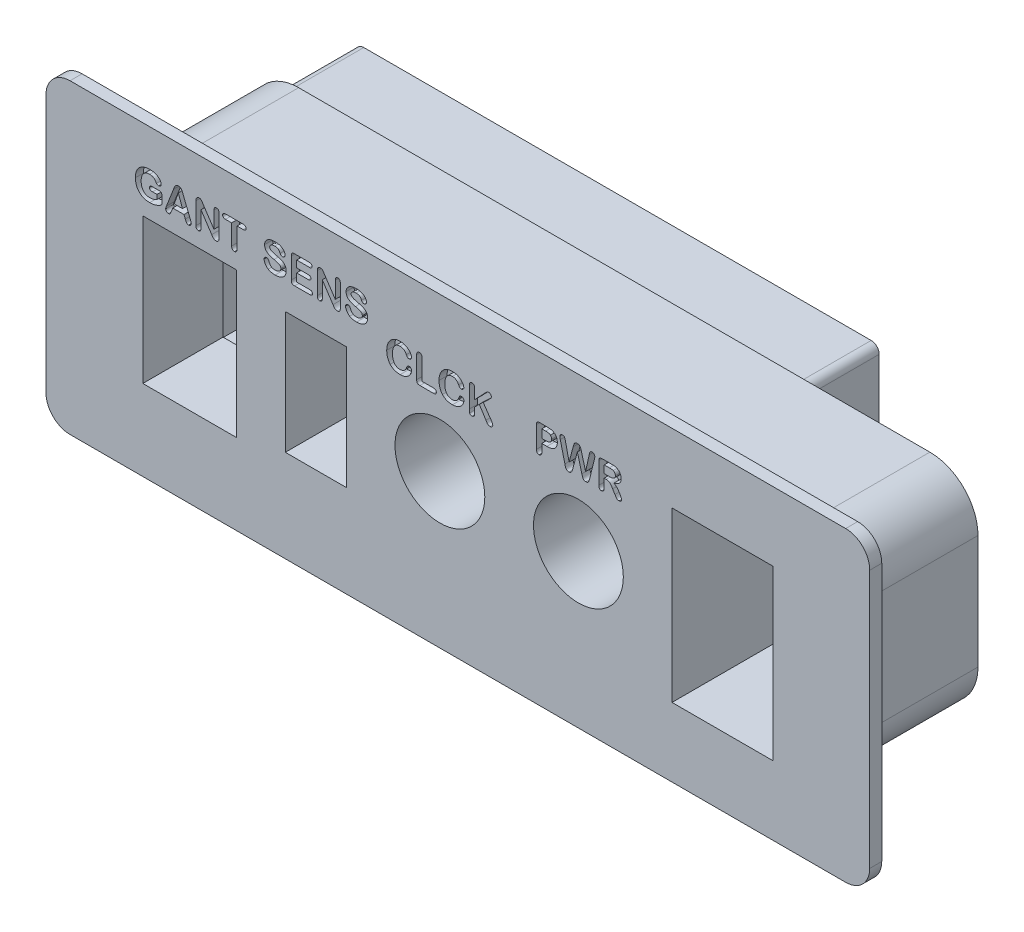
SolidWorks part; units mm, degrees
ref_plane "Front Plane" through (0, 0, 0) normal (0, 0, 1) x (1, 0, 0)
ref_plane "Top Plane" through (0, 0, 0) normal (0, 1, 0) x (1, 0, 0)
ref_plane "Right Plane" through (0, 0, 0) normal (1, 0, 0) x (0, 0, -1)
sketch "Sketch1" plane through (0, 0, 0) normal (0, 0, 1) x (1, 0, 0)
  line L1 (-45.35, -13.1) -> (45.35, -13.1)
  line L2 (-45.35, -13.1) -> (-45.35, 13.1)
  line L3 (-45.35, 13.1) -> (45.35, 13.1)
  line L4 (45.35, -13.1) -> (45.35, 13.1)
  line L5 (-45.35, -13.1) -> (45.35, 13.1) construction
  line L6 (-45.35, 13.1) -> (45.35, -13.1) construction
  point P0 (0, 0)
  dimension "D1" = 90.7
  dimension "D2" = 26.2
extrude "Boss-Extrude1" add sketch "Sketch1" against normal blind 18
sketch "Sketch2" plane through (0, 0, 0) normal (0, 0, 1) x (1, 0, 0)
  line L0 (-45.35, 13.1) -> (-45.35, -13.1) construction
  line L1 (-51.35, -19.1) -> (51.35, -19.1)
  line L2 (-51.35, -19.1) -> (-51.35, 19.1)
  line L3 (-51.35, 19.1) -> (51.35, 19.1)
  line L4 (51.35, -19.1) -> (51.35, 19.1)
  line L5 (-51.35, -19.1) -> (51.35, 19.1) construction
  line L6 (-51.35, 19.1) -> (51.35, -19.1) construction
  line L7 (45.35, 13.1) -> (-45.35, 13.1) construction
  point P0 (0, 0)
  dimension "D1" = 6
  dimension "D2" = 6
extrude "Boss-Extrude2" add sketch "Sketch2" along normal blind 1.5
fillet "Fillet1" radius 6 4 edges at (-45.35, 13.1, -9) (-45.35, -13.1, -9) (45.35, -13.1, -9) (45.35, 13.1, -9)
fillet "Fillet2" radius 3 4 edges at (51.35, -19.1, 0.75) (-51.35, -19.1, 0.75) (-51.35, 19.1, 0.75) (51.35, 19.1, 0.75)
sketch "Sketch3" plane through (0, 0, 1.5) normal (0, 0, 1) x (1, 0, 0)
  line L0 (-45.35, 13.1) -> (45.35, 13.1) construction
  line L1 (-45.35, 13.1) -> (-45.35, -13.1) construction
  line L2 (-45.35, -13.1) -> (45.35, -13.1) construction
  line L3 (45.35, 13.1) -> (45.35, -13.1) construction
  line L4 (-21.51, 7.6) -> (-13.91, 7.6)
  line L5 (-39.28, 9.05) -> (-27.58, 9.05)
  line L6 (-39.28, 9.05) -> (-39.28, -9.05)
  line L7 (-39.28, -9.05) -> (-27.58, -9.05)
  line L8 (-27.58, 9.05) -> (-27.58, -9.05)
  line L9 (-21.51, 7.6) -> (-21.51, -7.6)
  line L10 (-21.51, -7.6) -> (-13.91, -7.6)
  line L11 (-13.91, 7.6) -> (-13.91, -7.6)
  line L12 (-45.35, 0) -> (-39.28, 0) construction
  line L13 (-27.58, 0) -> (-21.51, 0) construction
  line L14 (20.63, 0) -> (26.7, 0) construction
  line L15 (-45.35, 13.1) -> (45.35, -13.1) construction
  line L16 (9.43, 0) -> (3.36, 0) construction
  line L17 (-7.84, 0) -> (-13.91, 0) construction
  line L18 (39.35, 13.1) -> (-39.35, 13.1) construction
  line L19 (39.3, -10.5) -> (26.7, -10.5)
  line L20 (39.3, -10.5) -> (39.3, 10.5)
  line L21 (39.3, 10.5) -> (26.7, 10.5)
  line L22 (26.7, -10.5) -> (26.7, 10.5)
  line L23 (39.3, -10.5) -> (26.7, 10.5) construction
  line L24 (39.3, 10.5) -> (26.7, -10.5) construction
  line L25 (45.35, -7.1) -> (45.35, 7.1) construction
  line L26 (39.3, 0) -> (45.35, 0) construction
  circle A0 centre (15.03, 0) radius 5.6
  circle A1 centre (-2.24, 0) radius 5.6
  point P20 (0, 0)
  point P23 (33, 0)
  dimension "D6" = 11.2
  dimension "D1" = 11.7
  dimension "D2" = 18.1
  dimension "D3" = 6.05
  dimension "D4" = 7.6
  dimension "D5" = 6.07
  dimension "D7" = 12.6
  dimension "D8" = 21
  dimension "D9" = 15.2
extrude "Cut-Extrude1" cut sketch "Sketch3" against normal through all
sketch "Sketch4" plane through (0, 0, 1.5) normal (0, 0, 1) x (1, 0, 0)
  line L0 (-33.43, -9.05) -> (-33.43, 10.95) construction
  line L1 (-39.28, -9.05) -> (-27.58, -9.05) construction
  line L2 (-17.71, -7.6) -> (-17.71, 12.4) construction
  line L3 (-21.51, -7.6) -> (-13.91, -7.6) construction
  line L4 (-40.43, 10.95) -> (-26.43, 10.95) construction
  line L5 (-24.71, 10.95) -> (-10.71, 10.95) construction
  line L6 (-2.24, 0) -> (-2.24, 8) construction
  line L7 (-12.74, 8) -> (8.26, 8) construction
  line L8 (15.03, 0) -> (15.03, 8) construction
  line L9 (4.53, 8) -> (25.53, 8) construction
  text T0 "GANT" font "Arial Rounded MT Bold" height in points 14
  text T1 "SENS" font "Arial Rounded MT Bold" height in points 14
  text T2 "CLCK" font "Arial Rounded MT Bold" height in points 14
  text T3 "PWR" font "Arial Rounded MT Bold" height in points 14
  point P11 (-33.43, 10.95)
  point P13 (-17.71, 10.95)
  point P22 (-2.24, 8)
  point P28 (15.03, 8)
  dimension "D1" = 20
  dimension "D2" = 14
  dimension "D3" = 21
  dimension "D4" = 8
extrude "Cut-Extrude2" cut sketch "Sketch4" against normal blind 1
sketch "Sketch5" plane through (0, 0, -18) normal (0, 0, -1) x (-1, 0, 0)
  line L7 (27.28, 9.4) -> (39.58, 9.4)
  line L8 (27.28, 9.4) -> (27.28, -9.4)
  line L9 (27.28, -9.4) -> (39.58, -9.4)
  line L10 (39.58, 9.4) -> (39.58, -9.4)
  line L11 (27.28, 9.4) -> (39.58, -9.4) construction
  line L12 (27.28, -9.4) -> (39.58, 9.4) construction
  line L14 (33.43, 0) -> (33.43, 9.05) construction
  line L15 (27.58, 9.05) -> (39.28, 9.05) construction
  line L18 (27.58, -9.05) -> (27.58, 9.05) construction
  point P5 (33.43, 0)
  point P23 (27.58, 0)
  dimension "D1" = 12.3
  dimension "D3" = 18.8
extrude "Cut-Extrude3" cut sketch "Sketch5" against normal blind 9.5
sketch "Sketch7" plane through (0, 0, -18) normal (0, 0, -1) x (-1, 0, 0)
  circle A0 centre (-15.03, 0) radius 5.9
  circle A1 centre (2.24, 0) radius 5.9
  dimension "D1" = 11.8
extrude "Cut-Extrude4" cut sketch "Sketch7" against normal blind 10
sketch "Sketch8" plane through (0, 0, -18) normal (0, 0, -1) x (-1, 0, 0)
  line L0 (10.875, 8.635) -> (-6.395, -8.635) construction
  line L1 (-23.665, 8.635) -> (-6.395, -8.635) construction
  circle A0 centre (-15.03, 0) radius 5.9 construction
  circle A1 centre (2.24, 0) radius 5.6 construction
  circle A2 centre (2.24, 0) radius 5.6 construction
  circle A3 centre (-6.395, -8.635) radius 2.15
  circle A5 centre (8.605, 6.365) radius 2.15
  point P9 (-15.03, 0)
  point P15 (2.24, 0)
  dimension "D1" = 4.3
  dimension "D2" = 15
extrude "Cut-Extrude5" cut sketch "Sketch8" against normal blind 10
sketch "Sketch9" plane through (0, 0, -18) normal (0, 0, -1) x (-1, 0, 0)
  line L0 (-20.03, 0) -> (-20.03, -11.5)
  line L1 (-10.03, 0) -> (-10.03, -11.5)
  line L2 (-2.76, 0) -> (-2.76, -11.5)
  line L3 (7.24, 0) -> (7.24, -11.5)
  line L4 (14.035, -11.5) -> (14.035, 7.6)
  line L5 (14.035, 7.6) -> (21.385, 7.6)
  line L6 (21.385, 7.6) -> (21.385, -11.5)
  line L7 (13.91, 7.6) -> (21.51, 7.6) construction
  line L15 (-20.03, -11.5) -> (-23.03, -11.5)
  line L16 (-23.03, -11.5) -> (-23.03, 11.5)
  line L17 (-23.03, 11.5) -> (42.23, 11.5)
  line L18 (27.28, -9.4) -> (39.58, -9.4) construction
  line L19 (39.58, 9.4) -> (27.28, 9.4) construction
  line L20 (24.5075, 0) -> (24.5075, 11.5) construction
  line L21 (39.23, -9.4) -> (27.63, 9.4) construction
  line L22 (39.23, 9.4) -> (27.63, -9.4) construction
  line L23 (33.43, 9.4) -> (33.43, -9.4) construction
  line L24 (27.63, -9.4) -> (27.63, -11.5)
  line L25 (27.63, 9.4) -> (27.63, -9.4)
  line L26 (39.23, -9.4) -> (27.63, -9.4)
  line L27 (39.23, 9.4) -> (39.23, -9.4)
  line L28 (39.23, 9.4) -> (27.63, 9.4)
  line L29 (39.23, -9.4) -> (39.23, -11.5)
  line L30 (42.23, 11.5) -> (42.23, -11.5)
  line L31 (42.23, -11.5) -> (39.23, -11.5)
  line L32 (27.28, -9.4) -> (39.58, -9.4) construction
  line L33 (27.63, -11.5) -> (21.385, -11.5)
  line L34 (14.035, -11.5) -> (7.24, -11.5)
  line L35 (-2.76, -11.5) -> (-10.03, -11.5)
  line L36 (-23.03, 0) -> (-15.03, 0) construction
  circle A0 centre (-15.03, 0) radius 5
  circle A1 centre (2.24, 0) radius 5
  circle A2 centre (-6.395, -8.635) radius 1.7
  circle A3 centre (8.605, 6.365) radius 1.7
  point P22 (17.71, 7.6)
  point P25 (17.71, 7.6)
  point P37 (33.43, -9.4)
  point P50 (33.43, 0)
  circle M8 centre (-6.395, -8.635) radius 2.15
  circle M9 centre (8.605, 6.365) radius 2.15
  circle M10 centre (-15.03, 0) radius 5.9
  circle M11 centre (2.24, 0) radius 5.9
  line M16 (39.58, 9.4) -> (39.58, -9.4)
  line M17 (39.58, -9.4) -> (27.28, -9.4)
  line M18 (27.28, -9.4) -> (27.28, 9.4)
  line M19 (27.28, 9.4) -> (39.58, 9.4)
  line M69 (21.51, 7.6) -> (21.51, -7.6)
  line M70 (21.51, -7.6) -> (13.91, -7.6)
  line M71 (13.91, -7.6) -> (13.91, 7.6)
  line M72 (13.91, 7.6) -> (21.51, 7.6)
  dimension "D1" = 10
  dimension "D2" = 3.4
  dimension "D3" = 11.6
  dimension "D4" = 23
  dimension "D5" = 3
  dimension "D6" = 7.35
  dimension "D7" = 3
extrude "Boss-Extrude3" add sketch "Sketch9" along normal blind 10 separate body contours L35 L2 L3 L34 L33 L24 L29 L31 L30 L17 L16 L15 L0 L1 M11 M17 M18 M19 M16 M10 M9 M8 | A0 L1 L0 M10 | A1 L3 L2 M11 | L25 M19 M18 M17 | L27 M19 M17 M16 | L4 M70 M72 M71 | L6 M72 M70 M69 region at (20.1786, -1.566, -18) region at (20.7219, -7.316, -18) region at (-0.6516, 5.5277, -18) region at (-39.405, 0, -18) region at (-27.455, 0, -18) region at (-13.9725, 0, -18) region at (-21.4475, 0, -18)
fillet "Fillet3" radius 1 16 edges at (-42.23, -11.5, -23) (-39.23, -11.5, -23) (-39.23, 9.4, -23) (-27.63, 9.4, -23) (-27.63, -11.5, -23) (-7.24, -11.5, -23) (2.76, -11.5, -23) (10.03, -11.5, -23) (20.03, -11.5, -23) (23.03, -11.5, -23) (23.03, 11.5, -23) (-42.23, 11.5, -23) (-21.385, -11.5, -23) (-14.035, -11.5, -23) (-21.385, 7.6, -23) (-14.035, 7.6, -23)
sketch "Sketch10" plane through (0, 0, 1.5) normal (0, 0, 1) x (1, 0, 0)
  line L0 (-21.51, 7.6) -> (-21.51, -7.6) construction
  line L1 (-21.51, -7.6) -> (-13.91, -7.6)
  line L2 (-21.51, -7.6) -> (-21.51, 7.6)
  line L3 (-21.51, 7.6) -> (-13.91, 7.6)
  line L4 (-13.91, -7.6) -> (-13.91, 7.6)
  line L5 (-21.51, -7.6) -> (-13.91, 7.6) construction
  line L6 (-21.51, 7.6) -> (-13.91, -7.6) construction
  line L7 (-13.91, 7.6) -> (-21.51, 7.6) construction
  point P0 (-17.71, 0)
  point P5 (-21.51, 0)
  point P6 (-17.71, 7.6)
  dimension "D1" = 15.2
  dimension "D2" = 7.6
equation "\"D2@Sketch1\"=26.2"
